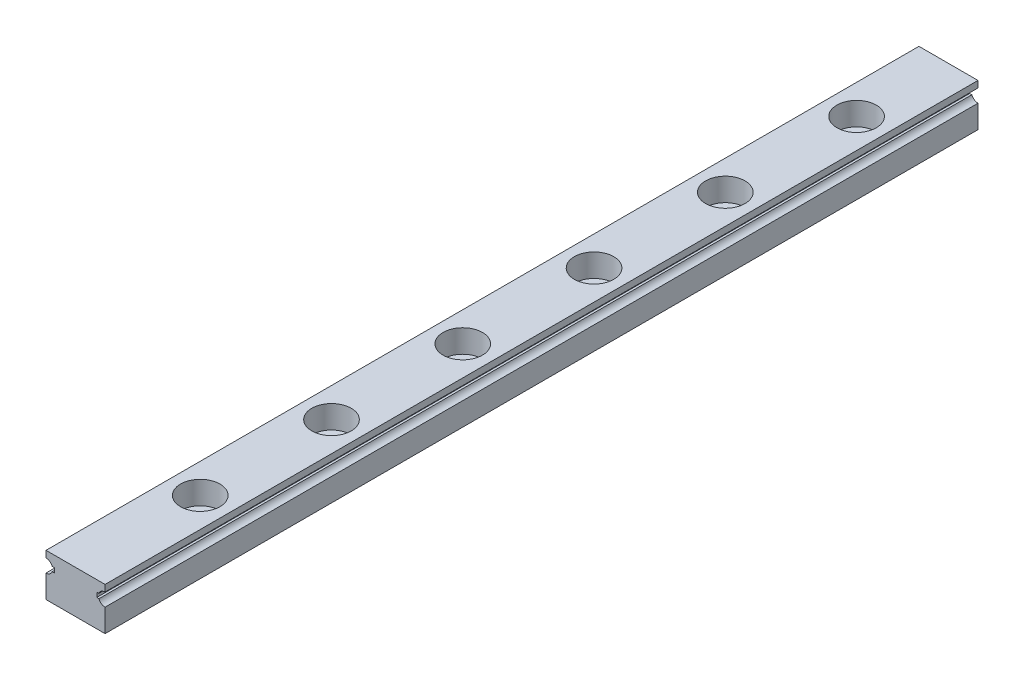
SolidWorks part; units mm, degrees
material "Сталь 40 ГОСТ 535-88"
ref_plane "Спереди" through (0, 0, 0) normal (0, 0, 1) x (1, 0, 0)
ref_plane "Сверху" through (0, 0, 0) normal (0, 1, 0) x (1, 0, 0)
ref_plane "Справа" through (0, 0, 0) normal (1, 0, 0) x (0, 0, -1)
sketch "Sketch1" plane through (0, 0, 0) normal (0, 0, 1) x (1, 0, 0)
  line L0 (0, 0) -> (0, 5.7299) construction
  line L1 (-4.5, -3.25) -> (4.5, -3.25)
  line L2 (-4.5, -3.25) -> (-4.5, 0.25)
  line L3 (-4.5, 3.25) -> (4.5, 3.25)
  line L4 (4.5, -3.25) -> (4.5, 0.25)
  line L5 (-4.5, -3.25) -> (4.5, 3.25) construction
  line L6 (-4.5, 3.25) -> (4.5, -3.25) construction
  line L7 (-4.5, 2.25) -> (-4.5, 3.25)
  line L8 (-3.564, 0.898) -> (-3.2351, 0.898)
  line L9 (3.564, 0.898) -> (3.2351, 0.898)
  line L10 (-3.564, 1.602) -> (-3.2351, 1.602)
  line L11 (-3.2351, 0.898) -> (-3.2351, 1.602)
  line L12 (3.2351, 0.898) -> (3.2351, 1.602)
  line L13 (3.564, 1.602) -> (3.2351, 1.602)
  line L14 (4.5, 2.25) -> (4.5, 3.25)
  arc A0 (-3.564, 1.602) -> (-4.5, 2.25) centre (-4.5, 1.25) ccw
  arc A1 (-4.5, 0.25) -> (-3.564, 0.898) centre (-4.5, 1.25) ccw
  arc A2 (4.5, 0.25) -> (3.564, 0.898) centre (4.5, 1.25) cw
  arc A3 (3.564, 1.602) -> (4.5, 2.25) centre (4.5, 1.25) cw
  point P0 (0, 0)
  dimension "D3" = 1
  dimension "D1" = 9
  dimension "D2" = 6.5
  dimension "D4" = 2
extrude "Extrude1" add sketch "Sketch1" along normal blind 133
sketch "Sketch2" plane through (0, 3.25, 0) normal (0, 1, 0) x (1, 0, 0)
  line L0 (4.5, 0) -> (-4.5, 0) construction
  circle A0 centre (0, -14) radius 1.75
  circle A1 centre (0, -14) radius 3
  dimension "D1" = 3.5
  dimension "D2" = 6
  dimension "D3" = 14
extrude "Extrude2" cut sketch "Sketch2" against normal blind 3.5 contours A1
extrude "Extrude3" cut sketch "Sketch" against normal through all contours A0
sketch "Sketch" plane through (0, 3.25, 0) normal (0, 1, 0) x (1, 0, 0) same geometry as "Sketch2"
pattern_linear "LPattern1" count 6 spacing 20 along (0, 0, 1) of "Extrude2", "Extrude3"
